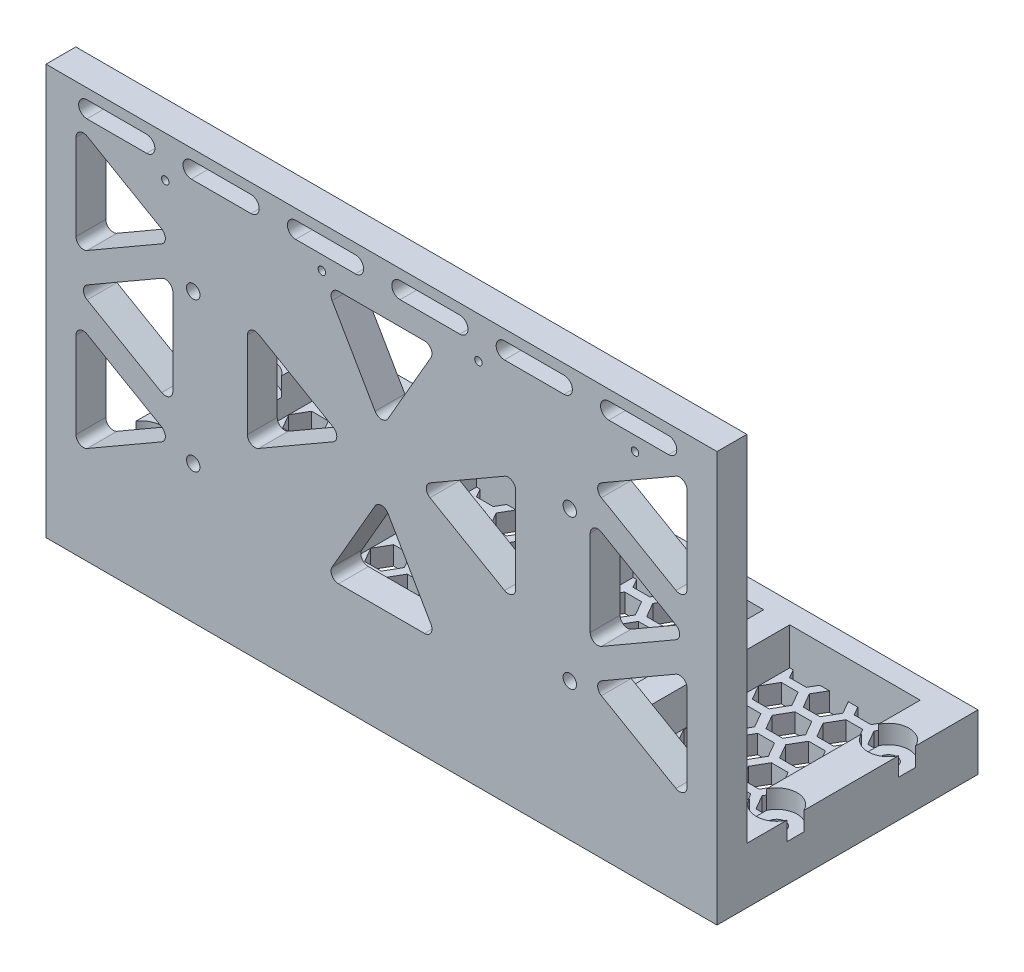
SolidWorks part; units mm, degrees
ref_plane "Front Plane" through (0, 0, 0) normal (0, 0, 1) x (1, 0, 0)
ref_plane "Top Plane" through (0, 0, 0) normal (0, 1, 0) x (1, 0, 0)
ref_plane "Right Plane" through (0, 0, 0) normal (1, 0, 0) x (0, 0, -1)
sketch "Sketch1" plane through (0, 0, 0) normal (0, 1, 0) x (1, 0, 0)
  line L1 (0, 0) -> (180, 0)
  line L2 (0, 0) -> (0, 70)
  line L3 (0, 70) -> (180, 70)
  line L4 (180, 0) -> (180, 70)
  dimension "D1" = 180
  dimension "D2" = 70
extrude "Boss-Extrude1" add sketch "Sketch1" along normal blind 15
ref_plane "Plane4" through (0, 15, 0) normal (0, 1, 0) x (1, 0, 0)
sketch "Sketch2" plane through (0, 15, 0) normal (0, 1, 0) x (1, 0, 0)
  line L0 (135, 8) -> (135, 64.5)
  line L1 (135, 8) -> (170, 8)
  line L2 (135, 64.5) -> (170, 64.5)
  line L3 (170, 64.5) -> (170, 8)
  line L4 (0, 0) -> (180, 0) construction
  line L6 (180, 0) -> (180, 70) construction
  dimension "D1" = 56.5
  dimension "D2" = 35
  dimension "D3" = 8
  dimension "D4" = 10
extrude "Cut-Extrude1" cut sketch "Sketch2" against normal blind 10
sketch "Sketch4" plane through (0, 0, -8) normal (0, 0, -1) x (-1, 0, 0)
  line L0 (-160.25, 8.75) -> (-160.25, 5)
  line L1 (-135, 5) -> (-170, 5) construction
  line L2 (-155.75, 8.75) -> (-155.75, 5)
  line L3 (-170, 5) -> (-170, 15) construction
  line L4 (-164.0648, 11) -> (-151.1193, 11) construction
  line L6 (-160.25, 5) -> (-155.75, 5)
  arc A0 (-155.75, 8.75) -> (-160.25, 8.75) centre (-158, 8.75) ccw
  dimension "D1" = 4.5
  dimension "D3" = 6
  dimension "D2" = 12
extrude "Boss-Extrude2" add sketch "Sketch4" along normal blind 4 contours L6 L2 A0 L0
pattern_linear "LPattern1" count 4 spacing 42 along (-1, 0, 0) of "Cut-Extrude1", "Boss-Extrude2"
sketch "Sketch5" plane through (0, 15, 0) normal (0, 1, 0) x (1, 0, 0)
  line L0 (180, 0) -> (180, 70) construction
  line L1 (0, 0) -> (180, 0)
  line L2 (0, 0) -> (0, 8)
  line L3 (0, 8) -> (180, 8)
  line L4 (180, 0) -> (180, 8)
extrude "Boss-Extrude3" add sketch "Sketch5" along normal blind 95
sketch "Sketch6" plane through (0, 0, 0) normal (0, 0, 1) x (1, 0, 0)
  line L0 (180, 110) -> (180, 0) construction
  line L1 (39.5, 36.9708) -> (140.5, 36.9708) construction
  line L2 (39.5, 36.9708) -> (39.5, 76.9708) construction
  line L3 (39.5, 76.9708) -> (140.5, 76.9708) construction
  line L4 (140.5, 36.9708) -> (140.5, 76.9708) construction
  line L5 (39.5, 36.9708) -> (140.5, 76.9708) construction
  line L6 (39.5, 76.9708) -> (140.5, 36.9708) construction
  circle A0 centre (39.5, 76.9708) radius 1.8
  circle A1 centre (140.5, 76.9708) radius 1.8
  circle A2 centre (39.5, 36.9708) radius 1.8
  circle A3 centre (140.5, 36.9708) radius 1.8
  point P4 (90, 56.9708)
  dimension "D3" = 3.6
  dimension "D1" = 101
  dimension "D2" = 40
  dimension "D4" = 39.5
extrude "Cut-Extrude2" cut sketch "Sketch6" against normal through all
chamfer "Chamfer1" distance 2 angle 45 4 edges at (41.3, 36.9708, -8) (41.3, 76.9708, -8) (142.3, 76.9708, -8) (142.3, 36.9708, -8)
sketch "Sketch8" plane through (0, 0, -8) normal (0, 0, -1) x (-1, 0, 0)
  line L0 (-180, 110) -> (-180, 15) construction
  line L1 (-180, 70.5) -> (0, 70.5) construction
  line L2 (-105, 28.5192) -> (-75, 28.5192)
  line L3 (-90, 70.5) -> (-105, 96.4808)
  line L4 (-105, 96.4808) -> (-75, 96.4808)
  line L5 (-75, 96.4808) -> (-90, 70.5)
  line L6 (0, 110) -> (0, 15) construction
  line L7 (-180, 110) -> (-180, 15) construction
  line L8 (-180, 62.5) -> (0, 62.5) construction
  line L9 (-90, 54.5) -> (-105, 28.5192)
  line L10 (-75, 28.5192) -> (-90, 54.5)
  line L11 (-90, 110) -> (-90, 14.9742) construction
  line L12 (-180, 110) -> (0, 110) construction
  line L14 (-54.0192, 47.5) -> (-54.0192, 77.5)
  line L15 (-80, 62.5) -> (-54.0192, 47.5)
  line L16 (-54.0192, 77.5) -> (-80, 62.5)
  line L17 (-100, 62.5) -> (-125.9808, 47.5)
  line L18 (-125.9808, 77.5) -> (-100, 62.5)
  line L19 (-125.9808, 47.5) -> (-125.9808, 77.5)
  line L20 (-135.9808, 110) -> (-135.9808, 15) construction
  line L21 (-180, 15) -> (0, 15) construction
  line L22 (-44.0192, 110) -> (-44.0192, 15) construction
  line L23 (-145.9808, 77.5) -> (-171.9615, 62.5)
  line L24 (-145.9808, 47.5) -> (-145.9808, 77.5)
  line L25 (-171.9615, 62.5) -> (-145.9808, 47.5)
  line L26 (-8.0385, 62.5) -> (-34.0192, 47.5)
  line L27 (-34.0192, 77.5) -> (-8.0385, 62.5)
  line L28 (-34.0192, 47.5) -> (-34.0192, 77.5)
  line L29 (-180, 37.5) -> (0, 37.5) construction
  line L30 (0, 85.5) -> (-180, 85.5) construction
  line L34 (-171.9615, 100.5) -> (-171.9615, 70.5)
  line L35 (-145.9808, 85.5) -> (-171.9615, 100.5)
  line L36 (-171.9615, 70.5) -> (-145.9808, 85.5)
  line L37 (-8.0385, 70.5) -> (-8.0385, 100.5)
  line L38 (-34.0192, 85.5) -> (-8.0385, 70.5)
  line L39 (-8.0385, 100.5) -> (-34.0192, 85.5)
  line L40 (-34.0192, 39.5) -> (-8.0385, 54.5)
  line L41 (-8.0385, 24.5) -> (-34.0192, 39.5)
  line L42 (-8.0385, 54.5) -> (-8.0385, 24.5)
  line L43 (-145.9808, 39.5) -> (-171.9615, 24.5)
  line L44 (-171.9615, 54.5) -> (-145.9808, 39.5)
  line L45 (-171.9615, 24.5) -> (-171.9615, 54.5)
  point P24 (-89.5, 15)
  dimension "D1" = 30
  dimension "D2" = 8
  dimension "D3" = 10
  dimension "D4" = 10
  dimension "D5" = 10
  dimension "D6" = 10
  dimension "D7" = 8
extrude "Cut-Extrude3" cut sketch "Sketch8" against normal blind 85 contours L23 L25 L24 | L34 L36 L35 | L45 L43 L44 | L19 L17 L18 | L5 L4 L3 | L14 L16 L15 | L2 L10 L9 | L42 L40 L41 | L28 L26 L27 | L37 L39 L38 region at (90, 37.1795, -8) region at (90, 87.8205, -8) region at (62.6795, 62.5, -8) region at (117.3205, 62.5, -8) region at (154.641, 62.5, -8) region at (25.359, 62.5, -8) region at (163.3013, 85.5, -8) region at (16.6987, 85.5, -8) region at (16.6987, 39.5, -8) region at (163.3013, 39.5, -8)
fillet "Fillet1" radius 2 30 edges at (145.9808, 85.5, -4) (8.0385, 54.5, -4) (34.0192, 77.5, -4) (54.0192, 77.5, -4) (90, 54.5, -4) (125.9808, 77.5, -4) (171.9615, 100.5, -4) (171.9615, 54.5, -4) (90, 70.5, -4) (8.0385, 100.5, -4) (145.9808, 77.5, -4) (75, 96.4808, -4) (8.0385, 62.5, -4) (145.9808, 39.5, -4) (100, 62.5, -4) (105, 96.4808, -4) (34.0192, 39.5, -4) (34.0192, 85.5, -4) (80, 62.5, -4) (171.9615, 62.5, -4) (145.9808, 47.5, -4) (75, 28.5192, -4) (54.0192, 47.5, -4) (8.0385, 70.5, -4) (8.0385, 24.5, -4) (34.0192, 47.5, -4) (171.9615, 70.5, -4) (125.9808, 47.5, -4) (105, 28.5192, -4) (171.9615, 24.5, -4)
sketch "Sketch9" plane through (0, 5, 0) normal (0, 1, 0) x (1, 0, 0)
  line L0 (9, 64.5) -> (9, 8) construction
  line L1 (13.5, -10) -> (13.5, -16.9018) construction
  line L2 (0, 0) -> (180, 0) construction
  line L71 (11.25, -10) -> (15.75, -10)
  line L72 (15.75, -10) -> (18, -13.8971)
  line L73 (18, -13.8971) -> (15.75, -17.7942)
  line L74 (15.75, -17.7942) -> (11.25, -17.7942)
  line L75 (11.25, -17.7942) -> (9, -13.8971)
  line L76 (9, -13.8971) -> (11.25, -10)
  line L83 (9, -13.8971) -> (18, -13.8971) construction
  line L220 (9, 8) -> (9, 64.5) construction
  line L221 (180, 8) -> (0, 8) construction
  line L222 (44, 64.5) -> (9, 64.5) construction
  line L223 (11.25, 0) -> (15.75, 0) [skipped]
  line L224 (15.75, 0) -> (18, -3.8971) [skipped]
  line L225 (18, -3.8971) -> (15.75, -7.7942) [skipped]
  line L226 (15.75, -7.7942) -> (11.25, -7.7942) [skipped]
  line L227 (11.25, -7.7942) -> (9, -3.8971) [skipped]
  line L228 (9, -3.8971) -> (11.25, 0) [skipped]
  line L229 (11.25, 10) -> (15.75, 10)
  line L230 (15.75, 10) -> (16.9047, 8)
  line L234 (10.0953, 8) -> (11.25, 10)
  line L235 (11.25, 20) -> (15.75, 20)
  line L236 (15.75, 20) -> (18, 16.1029)
  line L237 (18, 16.1029) -> (15.75, 12.2058)
  line L238 (15.75, 12.2058) -> (11.25, 12.2058)
  line L239 (11.25, 12.2058) -> (9, 16.1029)
  line L240 (9, 16.1029) -> (11.25, 20)
  line L241 (11.25, 30) -> (15.75, 30)
  line L242 (15.75, 30) -> (18, 26.1029)
  line L243 (18, 26.1029) -> (15.75, 22.2058)
  line L244 (15.75, 22.2058) -> (11.25, 22.2058)
  line L245 (11.25, 22.2058) -> (9, 26.1029)
  line L246 (9, 26.1029) -> (11.25, 30)
  line L247 (11.25, 40) -> (15.75, 40)
  line L248 (15.75, 40) -> (18, 36.1029)
  line L249 (18, 36.1029) -> (15.75, 32.2058)
  line L250 (15.75, 32.2058) -> (11.25, 32.2058)
  line L251 (11.25, 32.2058) -> (9, 36.1029)
  line L252 (9, 36.1029) -> (11.25, 40)
  line L253 (11.25, 50) -> (15.75, 50)
  line L254 (15.75, 50) -> (18, 46.1029)
  line L255 (18, 46.1029) -> (15.75, 42.2058)
  line L256 (15.75, 42.2058) -> (11.25, 42.2058)
  line L257 (11.25, 42.2058) -> (9, 46.1029)
  line L258 (9, 46.1029) -> (11.25, 50)
  line L259 (11.25, 60) -> (15.75, 60)
  line L260 (15.75, 60) -> (18, 56.1029)
  line L261 (18, 56.1029) -> (15.75, 52.2058)
  line L262 (15.75, 52.2058) -> (11.25, 52.2058)
  line L263 (11.25, 52.2058) -> (9, 56.1029)
  line L264 (9, 56.1029) -> (11.25, 60)
  line L267 (17.0746, 64.5) -> (15.75, 62.2058)
  line L268 (15.75, 62.2058) -> (11.25, 62.2058)
  line L269 (11.25, 62.2058) -> (9.9254, 64.5)
  line L271 (19.9103, 5) -> (24.4103, 5) [skipped]
  line L272 (24.4103, 5) -> (26.6603, 1.1029) [skipped]
  line L273 (26.6603, 1.1029) -> (24.4103, -2.7942) [skipped]
  line L274 (24.4103, -2.7942) -> (19.9103, -2.7942) [skipped]
  line L275 (19.9103, -2.7942) -> (17.6603, 1.1029) [skipped]
  line L276 (17.6603, 1.1029) -> (19.9103, 5) [skipped]
  line L277 (19.9103, 15) -> (24.4103, 15)
  line L278 (24.4103, 15) -> (26.6603, 11.1029)
  line L279 (26.6603, 11.1029) -> (24.8688, 8)
  line L281 (19.4517, 8) -> (17.6603, 11.1029)
  line L282 (17.6603, 11.1029) -> (19.9103, 15)
  line L283 (19.9103, 25) -> (24.4103, 25)
  line L284 (24.4103, 25) -> (26.6603, 21.1029)
  line L285 (26.6603, 21.1029) -> (24.4103, 17.2058)
  line L286 (24.4103, 17.2058) -> (19.9103, 17.2058)
  line L287 (19.9103, 17.2058) -> (17.6603, 21.1029)
  line L288 (17.6603, 21.1029) -> (19.9103, 25)
  line L289 (19.9103, 35) -> (24.4103, 35)
  line L290 (24.4103, 35) -> (26.6603, 31.1029)
  line L291 (26.6603, 31.1029) -> (24.4103, 27.2058)
  line L292 (24.4103, 27.2058) -> (19.9103, 27.2058)
  line L293 (19.9103, 27.2058) -> (17.6603, 31.1029)
  line L294 (17.6603, 31.1029) -> (19.9103, 35)
  line L295 (19.9103, 45) -> (24.4103, 45)
  line L296 (24.4103, 45) -> (26.6603, 41.1029)
  line L297 (26.6603, 41.1029) -> (24.4103, 37.2058)
  line L298 (24.4103, 37.2058) -> (19.9103, 37.2058)
  line L299 (19.9103, 37.2058) -> (17.6603, 41.1029)
  line L300 (17.6603, 41.1029) -> (19.9103, 45)
  line L301 (19.9103, 55) -> (24.4103, 55)
  line L302 (24.4103, 55) -> (26.6603, 51.1029)
  line L303 (26.6603, 51.1029) -> (24.4103, 47.2058)
  line L304 (24.4103, 47.2058) -> (19.9103, 47.2058)
  line L305 (19.9103, 47.2058) -> (17.6603, 51.1029)
  line L306 (17.6603, 51.1029) -> (19.9103, 55)
  line L308 (24.6989, 64.5) -> (26.6603, 61.1029)
  line L309 (26.6603, 61.1029) -> (24.4103, 57.2058)
  line L310 (24.4103, 57.2058) -> (19.9103, 57.2058)
  line L311 (19.9103, 57.2058) -> (17.6603, 61.1029)
  line L312 (17.6603, 61.1029) -> (19.6216, 64.5)
  line L313 (19.9103, 75) -> (24.4103, 75) [skipped]
  line L314 (24.4103, 75) -> (26.6603, 71.1029) [skipped]
  line L315 (26.6603, 71.1029) -> (24.4103, 67.2058) [skipped]
  line L316 (24.4103, 67.2058) -> (19.9103, 67.2058) [skipped]
  line L317 (19.9103, 67.2058) -> (17.6603, 71.1029) [skipped]
  line L318 (17.6603, 71.1029) -> (19.9103, 75) [skipped]
  line L319 (28.5705, 10) -> (33.0705, 10) [skipped]
  line L320 (33.0705, 10) -> (35.3205, 6.1029) [skipped]
  line L321 (35.3205, 6.1029) -> (33.0705, 2.2058) [skipped]
  line L322 (33.0705, 2.2058) -> (28.5705, 2.2058) [skipped]
  line L323 (28.5705, 2.2058) -> (26.3205, 6.1029) [skipped]
  line L324 (26.3205, 6.1029) -> (28.5705, 10) [skipped]
  line L325 (28.5705, 20) -> (33.0705, 20)
  line L326 (33.0705, 20) -> (35.3205, 16.1029)
  line L327 (35.3205, 16.1029) -> (33.0705, 12.2058)
  line L328 (33.0705, 12.2058) -> (28.5705, 12.2058)
  line L329 (28.5705, 12.2058) -> (26.3205, 16.1029)
  line L330 (26.3205, 16.1029) -> (28.5705, 20)
  line L331 (28.5705, 30) -> (33.0705, 30)
  line L332 (33.0705, 30) -> (35.3205, 26.1029)
  line L333 (35.3205, 26.1029) -> (33.0705, 22.2058)
  line L334 (33.0705, 22.2058) -> (28.5705, 22.2058)
  line L335 (28.5705, 22.2058) -> (26.3205, 26.1029)
  line L336 (26.3205, 26.1029) -> (28.5705, 30)
  line L337 (28.5705, 40) -> (33.0705, 40)
  line L338 (33.0705, 40) -> (35.3205, 36.1029)
  line L339 (35.3205, 36.1029) -> (33.0705, 32.2058)
  line L340 (33.0705, 32.2058) -> (28.5705, 32.2058)
  line L341 (28.5705, 32.2058) -> (26.3205, 36.1029)
  line L342 (26.3205, 36.1029) -> (28.5705, 40)
  line L343 (28.5705, 50) -> (33.0705, 50)
  line L344 (33.0705, 50) -> (35.3205, 46.1029)
  line L345 (35.3205, 46.1029) -> (33.0705, 42.2058)
  line L346 (33.0705, 42.2058) -> (28.5705, 42.2058)
  line L347 (28.5705, 42.2058) -> (26.3205, 46.1029)
  line L348 (26.3205, 46.1029) -> (28.5705, 50)
  line L349 (28.5705, 60) -> (33.0705, 60)
  line L350 (33.0705, 60) -> (35.3205, 56.1029)
  line L351 (35.3205, 56.1029) -> (33.0705, 52.2058)
  line L352 (33.0705, 52.2058) -> (28.5705, 52.2058)
  line L353 (28.5705, 52.2058) -> (26.3205, 56.1029)
  line L354 (26.3205, 56.1029) -> (28.5705, 60)
  line L357 (34.3951, 64.5) -> (33.0705, 62.2058)
  line L358 (33.0705, 62.2058) -> (28.5705, 62.2058)
  line L359 (28.5705, 62.2058) -> (27.2459, 64.5)
  line L361 (28.5705, 80) -> (33.0705, 80) [skipped]
  line L362 (33.0705, 80) -> (35.3205, 76.1029) [skipped]
  line L363 (35.3205, 76.1029) -> (33.0705, 72.2058) [skipped]
  line L364 (33.0705, 72.2058) -> (28.5705, 72.2058) [skipped]
  line L365 (28.5705, 72.2058) -> (26.3205, 76.1029) [skipped]
  line L366 (26.3205, 76.1029) -> (28.5705, 80) [skipped]
  line L367 (37.2308, 15) -> (41.7308, 15)
  line L368 (41.7308, 15) -> (43.9808, 11.1029)
  line L369 (43.9808, 11.1029) -> (42.1893, 8)
  line L371 (36.7722, 8) -> (34.9808, 11.1029)
  line L372 (34.9808, 11.1029) -> (37.2308, 15)
  line L373 (37.2308, 25) -> (41.7308, 25)
  line L374 (41.7308, 25) -> (43.9808, 21.1029)
  line L375 (43.9808, 21.1029) -> (41.7308, 17.2058)
  line L376 (41.7308, 17.2058) -> (37.2308, 17.2058)
  line L377 (37.2308, 17.2058) -> (34.9808, 21.1029)
  line L378 (34.9808, 21.1029) -> (37.2308, 25)
  line L379 (37.2308, 35) -> (41.7308, 35)
  line L380 (41.7308, 35) -> (43.9808, 31.1029)
  line L381 (43.9808, 31.1029) -> (41.7308, 27.2058)
  line L382 (41.7308, 27.2058) -> (37.2308, 27.2058)
  line L383 (37.2308, 27.2058) -> (34.9808, 31.1029)
  line L384 (34.9808, 31.1029) -> (37.2308, 35)
  line L385 (37.2308, 45) -> (41.7308, 45)
  line L386 (41.7308, 45) -> (43.9808, 41.1029)
  line L387 (43.9808, 41.1029) -> (41.7308, 37.2058)
  line L388 (41.7308, 37.2058) -> (37.2308, 37.2058)
  line L389 (37.2308, 37.2058) -> (34.9808, 41.1029)
  line L390 (34.9808, 41.1029) -> (37.2308, 45)
  line L391 (37.2308, 55) -> (41.7308, 55)
  line L392 (41.7308, 55) -> (43.9808, 51.1029)
  line L393 (43.9808, 51.1029) -> (41.7308, 47.2058)
  line L394 (41.7308, 47.2058) -> (37.2308, 47.2058)
  line L395 (37.2308, 47.2058) -> (34.9808, 51.1029)
  line L396 (34.9808, 51.1029) -> (37.2308, 55)
  line L398 (42.0194, 64.5) -> (43.9808, 61.1029)
  line L399 (43.9808, 61.1029) -> (41.7308, 57.2058)
  line L400 (41.7308, 57.2058) -> (37.2308, 57.2058)
  line L401 (37.2308, 57.2058) -> (34.9808, 61.1029)
  line L402 (34.9808, 61.1029) -> (36.9421, 64.5)
  line L403 (37.2308, 75) -> (41.7308, 75) [skipped]
  line L404 (41.7308, 75) -> (43.9808, 71.1029) [skipped]
  line L405 (43.9808, 71.1029) -> (41.7308, 67.2058) [skipped]
  line L406 (41.7308, 67.2058) -> (37.2308, 67.2058) [skipped]
  line L407 (37.2308, 67.2058) -> (34.9808, 71.1029) [skipped]
  line L408 (34.9808, 71.1029) -> (37.2308, 75) [skipped]
  line L409 (37.2308, 85) -> (41.7308, 85) [skipped]
  line L410 (41.7308, 85) -> (43.9808, 81.1029) [skipped]
  line L411 (43.9808, 81.1029) -> (41.7308, 77.2058) [skipped]
  line L412 (41.7308, 77.2058) -> (37.2308, 77.2058) [skipped]
  line L413 (37.2308, 77.2058) -> (34.9808, 81.1029) [skipped]
  line L414 (34.9808, 81.1029) -> (37.2308, 85) [skipped]
  line L415 (19.9103, -5) -> (24.4103, -5) [skipped]
  line L416 (24.4103, -5) -> (26.6603, -8.8971) [skipped]
  line L417 (26.6603, -8.8971) -> (24.4103, -12.7942) [skipped]
  line L418 (24.4103, -12.7942) -> (19.9103, -12.7942) [skipped]
  line L419 (19.9103, -12.7942) -> (17.6603, -8.8971) [skipped]
  line L420 (17.6603, -8.8971) -> (19.9103, -5) [skipped]
  line L421 (28.5705, 0) -> (33.0705, 0) [skipped]
  line L422 (33.0705, 0) -> (35.3205, -3.8971) [skipped]
  line L423 (35.3205, -3.8971) -> (33.0705, -7.7942) [skipped]
  line L424 (33.0705, -7.7942) -> (28.5705, -7.7942) [skipped]
  line L425 (28.5705, -7.7942) -> (26.3205, -3.8971) [skipped]
  line L426 (26.3205, -3.8971) -> (28.5705, 0) [skipped]
  line L427 (37.2308, 5) -> (41.7308, 5) [skipped]
  line L428 (41.7308, 5) -> (43.9808, 1.1029) [skipped]
  line L429 (43.9808, 1.1029) -> (41.7308, -2.7942) [skipped]
  line L430 (41.7308, -2.7942) -> (37.2308, -2.7942) [skipped]
  line L431 (37.2308, -2.7942) -> (34.9808, 1.1029) [skipped]
  line L432 (34.9808, 1.1029) -> (37.2308, 5) [skipped]
  line L433 (10.0953, 8) -> (16.9047, 8)
  line L435 (9.9254, 64.5) -> (17.0746, 64.5)
  line L437 (15.75, 70) -> (18, 66.1029) [skipped]
  line L438 (11.25, 70) -> (15.75, 70) [skipped]
  line L439 (9, 66.1029) -> (11.25, 70) [skipped]
  line L440 (19.6216, 64.5) -> (24.6989, 64.5)
  line L441 (19.9103, 65) -> (24.4103, 65) [skipped]
  line L442 (26.3205, 66.1029) -> (28.5705, 70) [skipped]
  line L443 (33.0705, 70) -> (35.3205, 66.1029) [skipped]
  line L444 (28.5705, 70) -> (33.0705, 70) [skipped]
  line L445 (36.9421, 64.5) -> (42.0194, 64.5)
  line L446 (27.2459, 64.5) -> (34.3951, 64.5)
  line L447 (37.2308, 65) -> (41.7308, 65) [skipped]
  line L448 (18, 6.1029) -> (15.75, 2.2058) [skipped]
  line L449 (11.25, 2.2058) -> (9, 6.1029) [skipped]
  line L450 (15.75, 2.2058) -> (11.25, 2.2058) [skipped]
  line L451 (19.4517, 8) -> (24.8688, 8)
  line L452 (24.4103, 7.2058) -> (19.9103, 7.2058) [skipped]
  line L453 (36.7722, 8) -> (42.1893, 8)
  line L454 (41.7308, 7.2058) -> (37.2308, 7.2058) [skipped]
  dimension "D2" = 120
  dimension "D3" = 10
  dimension "D4" = 9
  dimension "D5" = 4
  dimension "D11" = 120
sketch "Sketch10" plane through (0, 0, -8) normal (0, 0, -1) x (-1, 0, 0)
  line L0 (-158, 5) -> (-158, 100) construction
  line L1 (-160.25, 5) -> (-170, 5) construction
  circle A0 centre (-158, 99) radius 1
  dimension "D2" = 2
  dimension "D1" = 95
extrude "Cut-Extrude5" cut sketch "Sketch10" against normal through all
pattern_linear "LPattern3" count 4 spacing 42 along (-1, 0, 0) of "Cut-Extrude5"
sketch "Sketch11" plane through (0, 15, 0) normal (0, 1, 0) x (1, 0, 0)
  line L1 (4.5, 51) -> (175, 51) construction
  line L2 (4.5, 51) -> (4.5, 21) construction
  line L3 (4.5, 21) -> (175, 21) construction
  line L4 (175, 51) -> (175, 21) construction
  line L5 (4.5, 51) -> (175, 21) construction
  line L6 (4.5, 21) -> (175, 51) construction
  line L9 (4.5, 8) -> (4.5, 70) construction
  line L10 (9, 8) -> (0, 8) construction
  line L11 (180, 70) -> (0, 70) construction
  line L12 (175, 8) -> (175, 70) construction
  line L13 (180, 8) -> (170, 8) construction
  line L14 (180, 8) -> (0, 8) construction
  circle A0 centre (175, 51) radius 5.5
  circle A1 centre (175, 21) radius 5.5
  circle A2 centre (4.5, 21) radius 5.5
  circle A3 centre (4.5, 51) radius 5.5
  point P0 (89.75, 36)
  dimension "D1" = 11
  dimension "D2" = 30
  dimension "D3" = 13
extrude "Cut-Extrude6" cut sketch "Sketch11" against normal blind 5
sketch "Sketch12" plane through (0, 10, 0) normal (0, 1, 0) x (1, 0, 0)
  circle A0 centre (4.5, 51) radius 2.25
  circle A1 centre (4.5, 21) radius 2.25
  circle A2 centre (175, 51) radius 2.25
  circle A3 centre (175, 21) radius 2.25
  dimension "D1" = 4.5
extrude "Cut-Extrude7" cut sketch "Sketch12" against normal up to surface (10 mm away) up to face at (90, 0, -35)
extrude "Cut-Extrude8" cut sketch "Sketch9" against normal through all
pattern_linear "LPattern4" count 4 spacing 42 along (1, 0, 0) of "Cut-Extrude8"
sketch "Sketch13" plane through (0, 0, 0) normal (0, 0, 1) x (1, 0, 0)
  line L0 (0, 105) -> (180, 105) construction
  line L1 (0, 110) -> (0, 0) construction
  line L2 (180, 110) -> (180, 0) construction
  line L3 (0, 110) -> (180, 110) construction
  line L4 (10.9759, 105) -> (26.9759, 105) construction
  line L5 (10.9759, 107.2196) -> (26.9759, 107.2196)
  line L6 (10.9759, 102.7804) -> (26.9759, 102.7804)
  arc A0 (10.9759, 107.2196) -> (10.9759, 102.7804) centre (10.9759, 105) ccw
  arc A1 (26.9759, 102.7804) -> (26.9759, 107.2196) centre (26.9759, 105) ccw
  point P10 (18.9759, 105)
  dimension "D1" = 5
  dimension "D2" = 16
extrude "Cut-Extrude9" cut sketch "Sketch13" against normal through all
pattern_linear "LPattern5" count 6 spacing 28 along (1, 0, 0) of "Cut-Extrude9"
